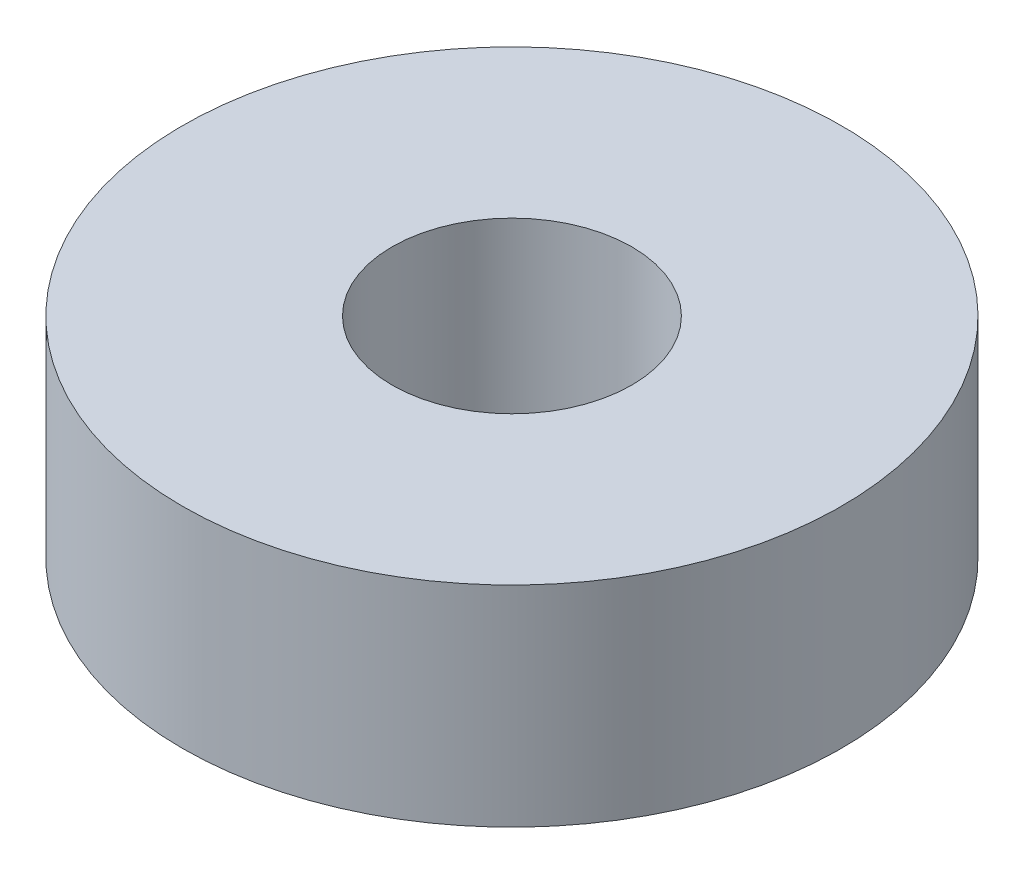
SolidWorks part; units mm, degrees
ref_plane "Front Plane" through (0, 0, 0) normal (0, 0, 1) x (1, 0, 0)
ref_plane "Top Plane" through (0, 0, 0) normal (0, 1, 0) x (1, 0, 0)
ref_plane "Right Plane" through (0, 0, 0) normal (1, 0, 0) x (0, 0, -1)
sketch "Sketch1" plane through (0, 0, 0) normal (0, 1, 0) x (1, 0, 0)
  circle A0 centre (0, 0) radius 11
  circle A1 centre (0, 0) radius 4
  dimension "D1" = 22
  dimension "D2" = 8
extrude "Boss-Extrude1" add sketch "Sketch1" along normal blind 3.5 and the other way blind 3.5
